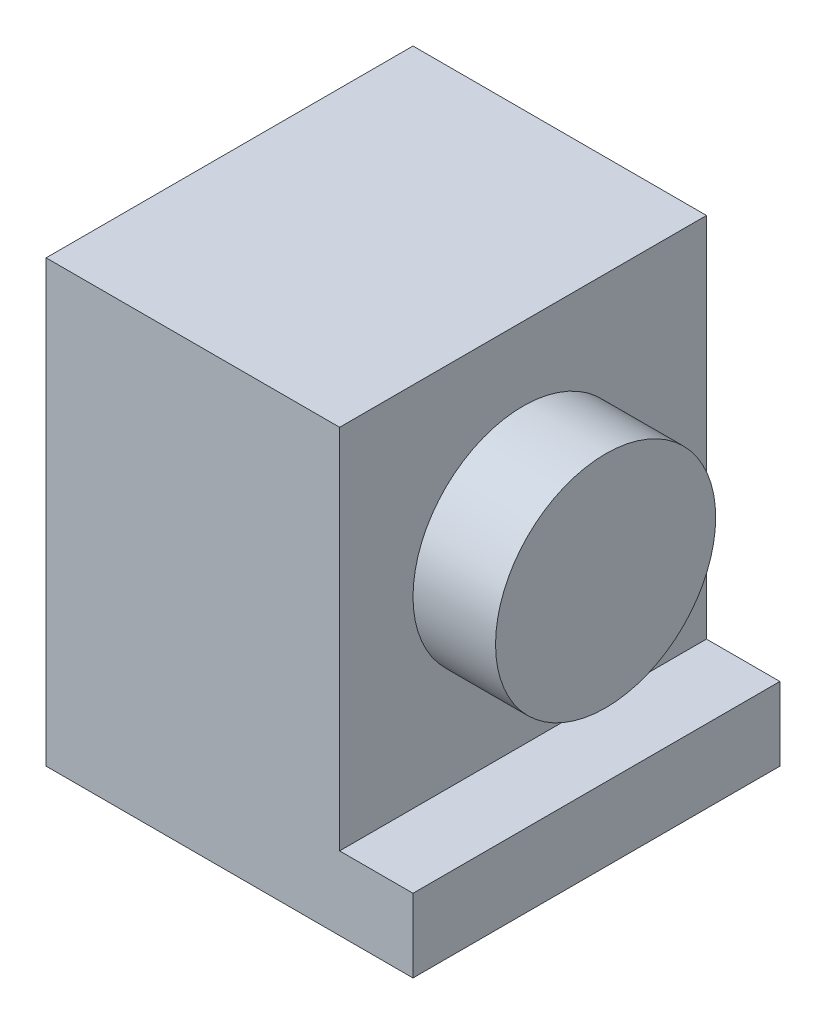
SolidWorks part; units mm, degrees
ref_plane "Спереди" through (0, 0, 0) normal (0, 0, 1) x (1, 0, 0)
ref_plane "Сверху" through (0, 0, 0) normal (0, 1, 0) x (1, 0, 0)
ref_plane "Справа" through (0, 0, 0) normal (1, 0, 0) x (0, 0, -1)
sketch "Эскиз1" plane through (0, 0, 0) normal (0, 1, 0) x (1, 0, 0)
  line L1 (4, -4) -> (-4, -4)
  line L2 (4, -4) -> (4, 4)
  line L3 (4, 4) -> (-4, 4)
  line L4 (-4, -4) -> (-4, 4)
  line L5 (4, -4) -> (-4, 4) construction
  line L6 (4, 4) -> (-4, -4) construction
  point P0 (0, 0)
  dimension "D1" = 8
  dimension "D2" = 8
extrude "Бобышка-Вытянуть1" add sketch "Эскиз1" along normal blind 9.6
sketch "Эскиз2" plane through (0, 9.6, 0) normal (0, 1, 0) x (1, 0, 0)
  line L0 (4, 4) -> (-4, 4) construction
  line L1 (2.4, 4) -> (4, 4)
  line L2 (2.4, 4) -> (2.4, -4)
  line L3 (2.4, -4) -> (4, -4)
  line L4 (4, 4) -> (4, -4)
  dimension "D1" = 1.6
extrude "Вырез-Вытянуть1" cut sketch "Эскиз2" against normal blind 8
sketch "Эскиз5" plane through (2.4, 0, 0) normal (1, 0, 0) x (0, 0, -1)
  line L0 (-4, 9.6) -> (4, 1.6)
  line L1 (4, 1.6) -> (-4, 1.6) construction
  line L2 (4, 9.6) -> (-4, 1.6)
  circle A0 centre (0, 5.6) radius 2.4
extrude "Бобышка-Вытянуть2" add sketch "Эскиз5" along normal blind 1.8 contours A0
